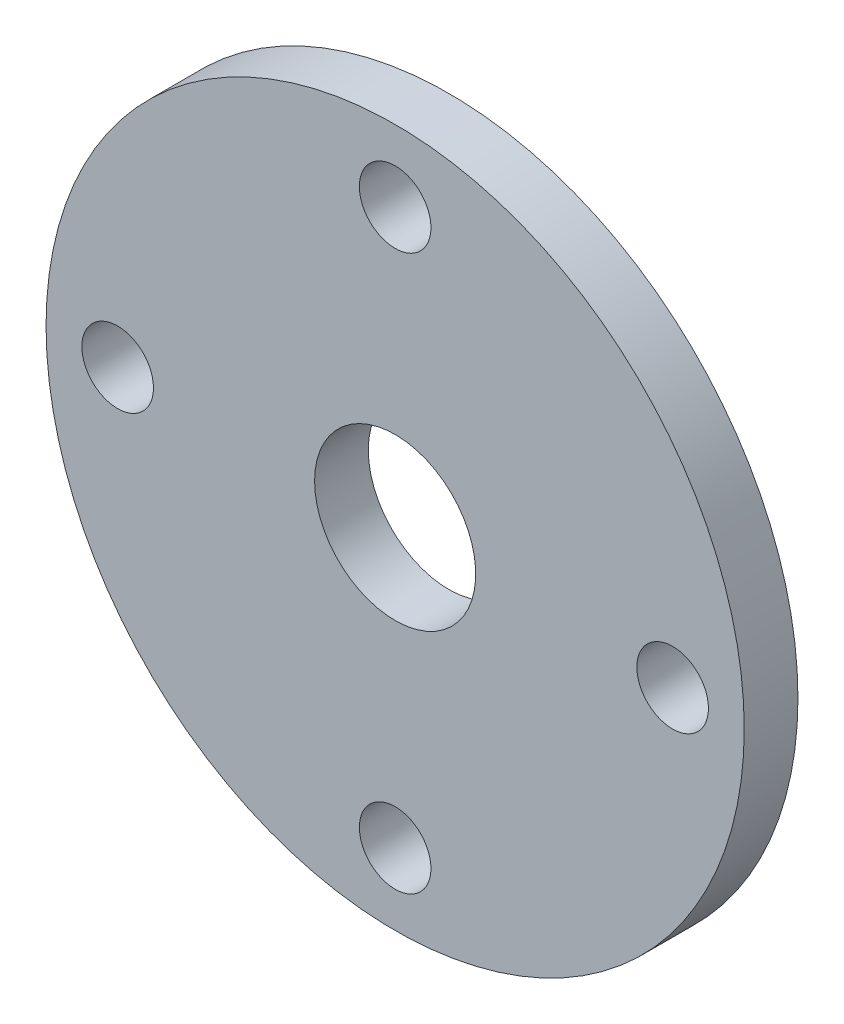
SolidWorks part; units mm, degrees
ref_plane "Alzado" through (0, 0, 0) normal (0, 0, 1) x (1, 0, 0)
ref_plane "Planta" through (0, 0, 0) normal (0, 1, 0) x (1, 0, 0)
ref_plane "Vista lateral" through (0, 0, 0) normal (1, 0, 0) x (0, 0, -1)
sketch "Croquis1" plane through (0, 0, 0) normal (0, 0, 1) x (1, 0, 0)
  circle A0 centre (0, 0) radius 19.5
  circle A1 centre (0, -15.5) radius 2
  circle A2 centre (15.5, 0) radius 2
  circle A3 centre (0, 15.5) radius 2
  circle A4 centre (-15.5, 0) radius 2
  dimension "D1" = 39
  dimension "D6" = 4
  dimension "D7" = 4
  dimension "D8" = 4
  dimension "D9" = 4
  dimension "D2" = 15.5
  dimension "D3" = 15.5
  dimension "D4" = 15.5
  dimension "D5" = 15.5
extrude "Saliente-Extruir1" add sketch "Croquis1" along normal blind 3
sketch "Croquis4" plane through (0, 0, 0) normal (0, 0, -1) x (-1, 0, 0)
  circle A0 centre (0, 0) radius 4.5
  dimension "D1" = 9
extrude "Cortar-Extruir1" cut sketch "Croquis4" against normal blind 1
extrude "Cortar-Extruir2" cut sketch "Croquis4<2>" against normal blind 3
sketch "Croquis4<2>" plane through (0, 0, 0) normal (0, 0, -1) x (-1, 0, 0) same geometry as "Croquis4"
